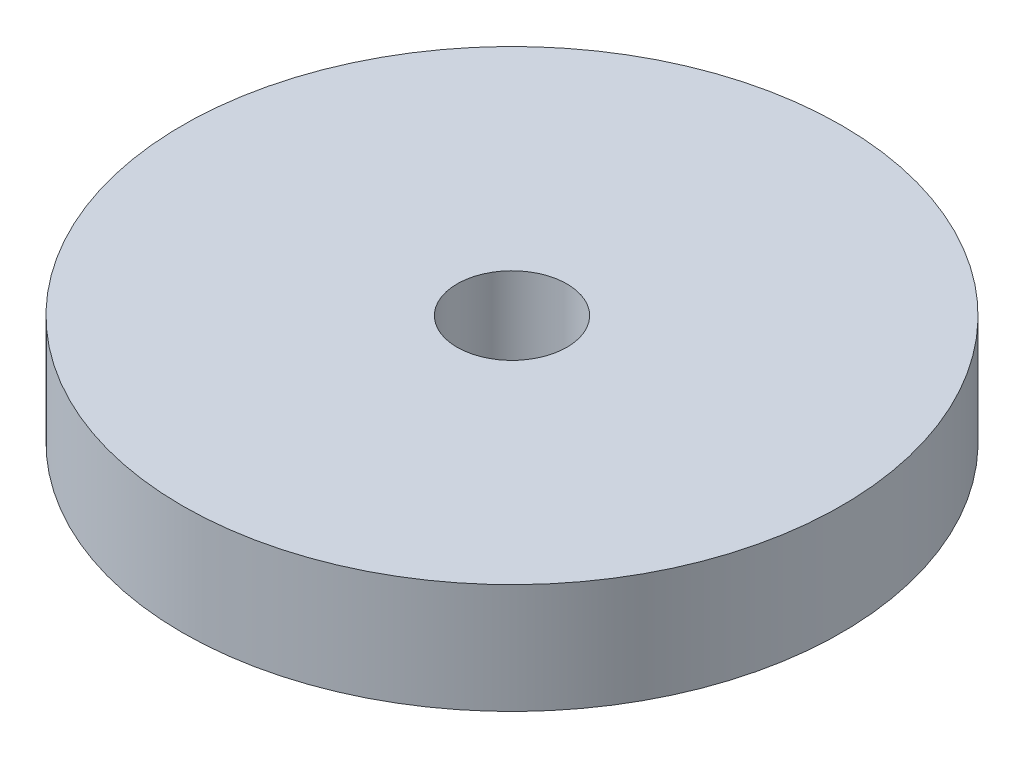
SolidWorks part; units mm, degrees
material "Natural Rubber"
ref_plane "Front Plane" through (0, 0, 0) normal (0, 0, 1) x (1, 0, 0)
ref_plane "Top Plane" through (0, 0, 0) normal (0, 1, 0) x (1, 0, 0)
ref_plane "Right Plane" through (0, 0, 0) normal (1, 0, 0) x (0, 0, -1)
sketch "Sketch1" plane through (0, 0, 0) normal (0, 1, 0) x (1, 0, 0)
  circle A0 centre (0, 0) radius 150
  dimension "D1" = 300
sketch "Sketch2" plane through (0, 0, 0) normal (0, 1, 0) x (1, 0, 0)
  circle A0 centre (0, 0) radius 25
  dimension "D1" = 50
extrude "Boss-Extrude1" add sketch "Sketch1" along normal blind 25 and the other way blind 25 contours A0
extrude "Cut-Extrude2" cut sketch "Sketch2" against normal through all both and the other way through all
sketch "Sketch5" plane through (0, 0, 0) normal (1, 0, 0) x (0, 0, -1)
  line L0 (0, 0) -> (0, 15) construction
  line L1 (0, 0) -> (0, -15) construction
  dimension "D1" = 30
  dimension "D2" = 15
